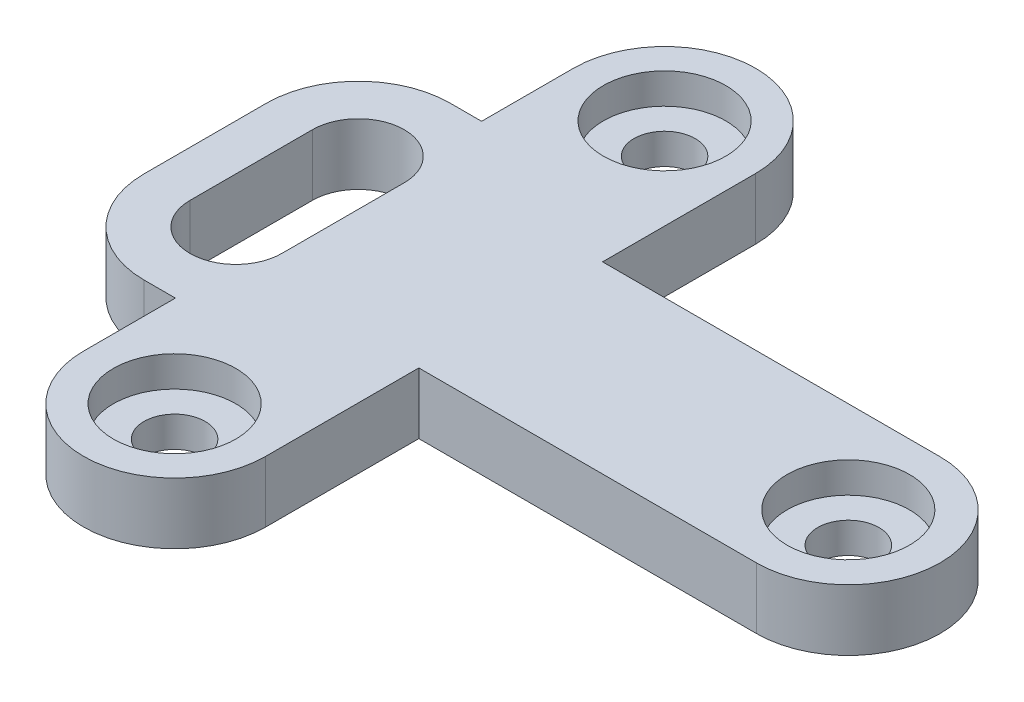
SolidWorks part; units mm, degrees
ref_plane "Front Plane" through (0, 0, 0) normal (0, 0, 1) x (1, 0, 0)
ref_plane "Top Plane" through (0, 0, 0) normal (0, 1, 0) x (1, 0, 0)
ref_plane "Right Plane" through (0, 0, 0) normal (1, 0, 0) x (0, 0, -1)
sketch "Sketch3" plane through (0, 0, 0) normal (0, 1, 0) x (1, 0, 0)
  line L0 (-57.3593, 0) -> (103.6583, 0) construction
  line L1 (-49.7988, 40) -> (44.7614, 40) construction
  line L2 (58.1512, -16.8065) -> (58.1512, 27.4915) construction
  line L3 (58.1512, 15) -> (3.0264, 15)
  line L4 (-11.8488, -68.4363) -> (-11.8488, 71.9216) construction
  line L5 (3.0264, 40) -> (3.0264, 15)
  line L6 (3.0264, -40) -> (3.0264, -15)
  line L7 (58.1512, -15) -> (3.0264, -15)
  line L8 (-26.724, 40) -> (-26.724, 25)
  line L9 (-31.8488, -46.5231) -> (-31.8488, 53.5976) construction
  line L10 (-55.9681, 10) -> (-19.8868, 10) construction
  line L11 (-39.3488, 10) -> (-39.3488, -10)
  line L12 (-16.8488, -10) -> (-55.9681, -10) construction
  line L13 (-24.3488, 10) -> (-24.3488, -10)
  line L14 (-46.8488, 10) -> (-46.8488, -10)
  line L15 (-26.724, -25) -> (-26.724, -40)
  line L16 (-31.8488, 25) -> (-26.724, 25)
  line L17 (-31.8488, -25) -> (-26.724, -25)
  circle A0 centre (58.1512, 0) radius 10
  circle A2 centre (58.1512, 0) radius 5
  arc A3 (58.1512, -15) -> (58.1512, 15) centre (58.1512, 0) ccw
  circle A4 centre (-11.8488, 40) radius 5
  circle A5 centre (-11.8488, 40) radius 10
  arc A6 (3.0264, 40) -> (-26.724, 40) centre (-11.8488, 40) ccw
  circle A7 centre (-11.8488, -40) radius 10
  circle A8 centre (-11.8488, -40) radius 5
  arc A9 (3.0264, -40) -> (-26.724, -40) centre (-11.8488, -40) cw
  arc A10 (-24.3488, 10) -> (-39.3488, 10) centre (-31.8488, 10) ccw
  arc A11 (-39.3488, -10) -> (-24.3488, -10) centre (-31.8488, -10) ccw
  arc A13 (-46.8488, -10) -> (-31.8488, -25) centre (-31.8488, -10) ccw
  arc A14 (-31.8488, 25) -> (-46.8488, 10) centre (-31.8488, 10) ccw
  dimension "D2" = 20
  dimension "D3" = 10
  dimension "D4" = 20
  dimension "D6" = 10
  dimension "D5" = 20
extrude "Boss-Extrude1" add sketch "Sketch3" along normal blind 10 contours L16 A14 L14 A13 L17 L15 A9 L6 L7 A3 L3 L5 A6 L8 A7 A5 A0 A11 L11 A10 L13 region at (1.8577, 0, 0)
extrude "Boss-Extrude3" add sketch "Sketch3<5>" along normal blind 5 contours A5 A4 | A7 A8 | A0 A2 region at (48.434, 0, 0) region at (-21.566, 0, -40) region at (-21.566, 0, 40)
sketch "Sketch3<5>" plane through (0, 0, 0) normal (0, 1, 0) x (1, 0, 0) same geometry as "Sketch3"
